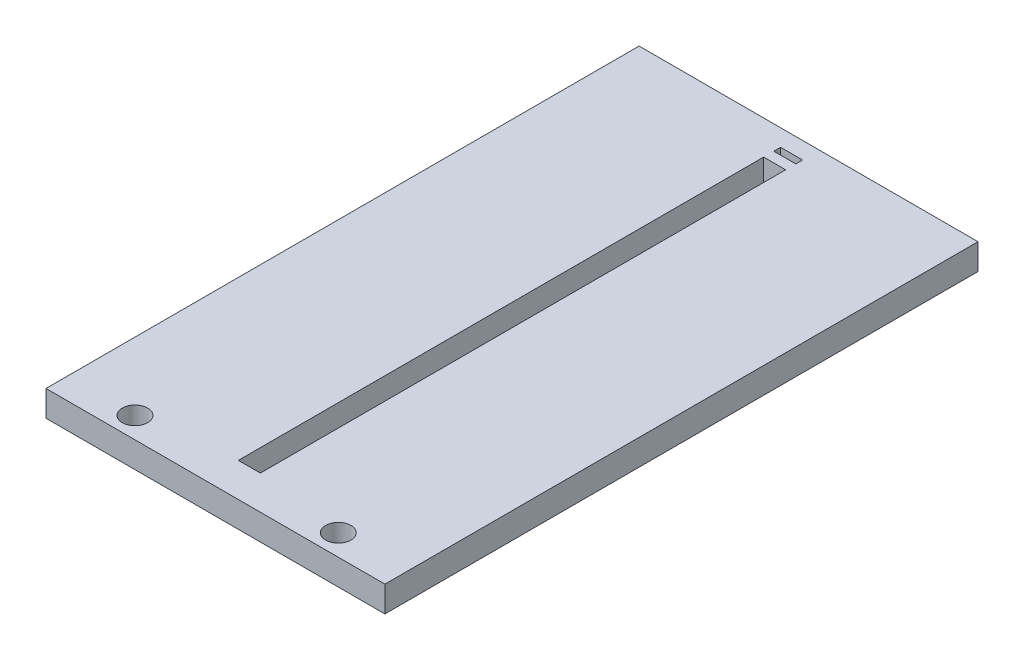
SolidWorks part; units mm, degrees
ref_plane "Front Plane" through (0, 0, 0) normal (0, 0, 1) x (1, 0, 0)
ref_plane "Top Plane" through (0, 0, 0) normal (0, 1, 0) x (1, 0, 0)
ref_plane "Right Plane" through (0, 0, 0) normal (1, 0, 0) x (0, 0, -1)
sketch "Sketch1" plane through (0, 0, 0) normal (0, 1, 0) x (1, 0, 0)
  line L1 (0, 0) -> (40, 0)
  line L2 (0, 0) -> (0, 70)
  line L3 (0, 70) -> (40, 70)
  line L4 (40, 0) -> (40, 70)
  dimension "D1" = 40
  dimension "D2" = 70
extrude "Boss-Extrude1" add sketch "Sketch1" along normal blind 3.05 contours L2 | L1 L4 L3 L2 | L4 region at (20, 0, -35)
sketch "Sketch4" plane through (0, 3.05, 0) normal (0, 1, 0) x (1, 0, 0)
  line L0 (20, 70) -> (20, 68)
  line L1 (0, 70) -> (40, 70) construction
  line L2 (20, 4) -> (20, 0)
  line L3 (21.3, 68) -> (18.7, 68)
  line L4 (18.7, 68) -> (18.7, 67.2)
  line L5 (18.7, 67.2) -> (21.3, 67.2)
  line L6 (21.3, 67.2) -> (21.3, 68)
  line L7 (20, 67.2) -> (20, 66)
  line L8 (0, 0) -> (40, 0) construction
  line L9 (21.3, 66) -> (18.7, 66)
  line L10 (18.7, 66) -> (18.7, 4)
  line L11 (18.7, 4) -> (21.3, 4)
  line L12 (21.3, 4) -> (21.3, 66)
  point P10 (20, 68)
  point P22 (20, 66)
  dimension "D1" = 2
  dimension "D2" = 0.8
  dimension "D3" = 1.2
  dimension "D4" = 2.6
  dimension "D5" = 4
  dimension "D6" = 2.6
extrude "Cut-Extrude1" cut sketch "Sketch4" against normal blind 10 contours L11 L12 L9 L10 | L5 L6 L3 L4 region at (20, 3.05, -67.6) region at (20, 3.05, -35)
sketch "Sketch5" plane through (0, 3.05, 0) normal (0, 1, 0) x (1, 0, 0)
  line L0 (0, 70) -> (0, 30)
  line L1 (0, 0) -> (0, 70) construction
  line L2 (0, 70) -> (15, 70)
  line L3 (0, 70) -> (40, 70) construction
  line L5 (40, 70) -> (25, 70)
  line L6 (40, 70) -> (40, 30)
  line L7 (40, 0) -> (40, 70) construction
  line L9 (15, 70) -> (15, 30)
  line L10 (15, 30) -> (0, 30)
  line L11 (25, 70) -> (25, 30)
  line L12 (25, 30) -> (40, 30)
  circle A0 centre (7.5, 37.5) radius 7.5
  circle A1 centre (32.5, 37.5) radius 7.5
  line M14 (40, 0) -> (40, 70)
  line M15 (40, 70) -> (0, 70)
  line M16 (0, 70) -> (0, 0)
  dimension "D1" = 40
  dimension "D2" = 15
  dimension "D3" = 40
  dimension "D4" = 15
extrude "Cut-Extrude2" [suppressed] cut sketch "Sketch5" against normal blind 10 contours A0 L9 M15 M16 | A0 | A0 L0 L10 | A1 L6 L11 M15 | A1 | A1 L12 M14
sketch "Sketch7" plane through (0, 3.05, 0) normal (0, 1, 0) x (1, 0, 0)
  line L0 (0, 0) -> (8, 0)
  line L1 (0, 0) -> (40, 0) construction
  line L2 (8, 0) -> (8, 2.5)
  line L3 (8, 2.5) -> (32, 2.5)
  circle A0 centre (8, 2.5) radius 1.5
  circle A1 centre (32, 2.5) radius 1.5
  dimension "D3" = 3
  dimension "D5" = 3
  dimension "D1" = 8
  dimension "D2" = 2.5
  dimension "D4" = 24
extrude "Cut-Extrude4" cut sketch "Sketch7" against normal blind 10 contours L3 A0 L2 | L2 A0 L3 | A1 region at (7.7878, 3.05, -2.7122) region at (32, 3.05, -3.9576) region at (8.6366, 3.05, -1.8634)
sketch "Sketch9" plane through (0, 0, -66) normal (0, 0, 1) x (1, 0, 0)
  line L0 (20, 3.05) -> (20, 0) construction
  line L1 (0, 3.05) -> (40, 3.05) construction
  line L2 (0, 0) -> (40, 0) construction
  circle A0 centre (20, 1.525) radius 1.525
